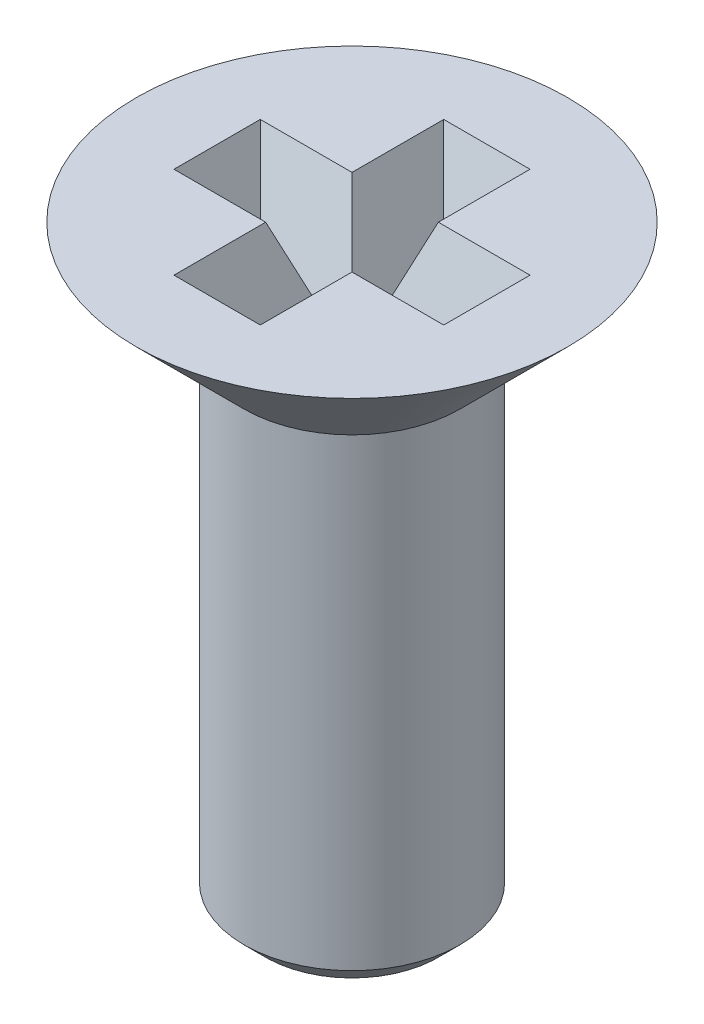
SolidWorks part; units mm, degrees
material "Plain Carbon Steel"
ref_plane "Front Plane" through (0, 0, 0) normal (0, 0, 1) x (1, 0, 0)
ref_plane "Top Plane" through (0, 0, 0) normal (0, 1, 0) x (1, 0, 0)
ref_plane "Right Plane" through (0, 0, 0) normal (1, 0, 0) x (0, 0, -1)
sketch "Sketch1" plane through (0, 0, 0) normal (0, 0, 1) x (1, 0, 0)
  line L0 (0, 0) -> (1, 0)
  line L1 (1, 0) -> (1, 4.5)
  line L2 (1, 4.5) -> (2, 5.5)
  line L3 (2, 5.5) -> (0, 5.5)
  line L4 (0, 5.5) -> (0, 0)
  dimension "D1" = 1
  dimension "D2" = 5.5
  dimension "D3" = 45
  dimension "D4" = 2
revolve "Revolve1" add sketch "Sketch1" angle 360 about L4
chamfer "Chamfer1" distance 0.2 angle 45 1 edges at (-1, 0, 0)
sketch "Sketch2" plane through (0, 5.5, 0) normal (0, 1, 0) x (1, 0, 0)
  line L1 (-1.25, -0.4) -> (1.25, -0.4)
  line L2 (-1.25, -0.4) -> (-1.25, 0.4)
  line L3 (-1.25, 0.4) -> (1.25, 0.4)
  line L4 (1.25, -0.4) -> (1.25, 0.4)
  line L5 (-1.25, -0.4) -> (1.25, 0.4) construction
  line L6 (-1.25, 0.4) -> (1.25, -0.4) construction
  point P0 (0, 0)
  dimension "D1" = 0.8
  dimension "D2" = 2.5
extrude "Cut-Extrude1" cut sketch "Sketch2" against normal blind 1 draft 20
ref_axis "Axis1" through (0, 0.2, 0) along (0, 1, 0)
pattern_circular "CirPattern1" count 2 every 90 about axis through (0, 0.2, 0) along (0, 1, 0) of "Cut-Extrude1"
